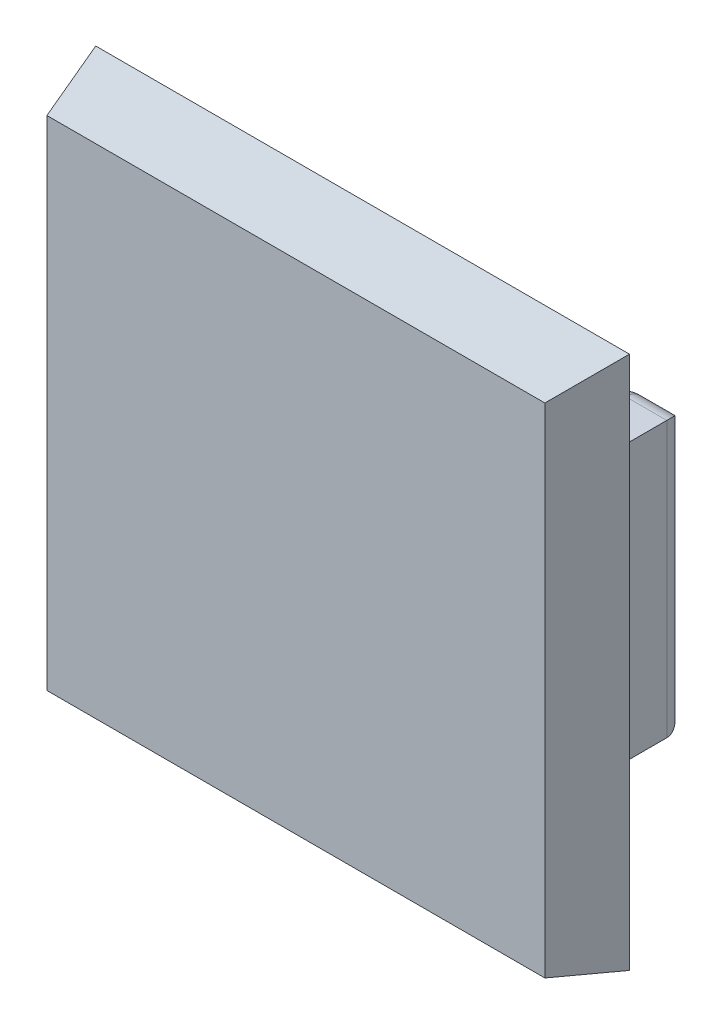
SolidWorks part; units mm, degrees
ref_plane "Front Plane" through (0, 0, 0) normal (0, 0, 1) x (1, 0, 0)
ref_plane "Top Plane" through (0, 0, 0) normal (0, 1, 0) x (1, 0, 0)
ref_plane "Right Plane" through (0, 0, 0) normal (1, 0, 0) x (0, 0, -1)
sketch "Sketch1" plane through (0, 0, 0) normal (0, 0, 1) x (1, 0, 0)
  line L1 (-10, 10) -> (10, 10)
  line L2 (-10, 10) -> (-10, -10)
  line L3 (-10, -10) -> (10, -10)
  line L4 (10, 10) -> (10, -10)
  line L5 (-10, 10) -> (10, -10) construction
  line L6 (-10, -10) -> (10, 10) construction
  point P0 (0, 0)
  dimension "D1" = 20
  dimension "D2" = 20
extrude "Boss-Extrude1" add sketch "Sketch1" along normal blind 2.5 draft 15
sketch "Sketch2" plane through (0, 0, 0) normal (0, 0, -1) x (-1, 0, 0)
  line L0 (10, 10) -> (10, -10) construction
  line L1 (-9, 9) -> (9, 9)
  line L2 (-9, 9) -> (-9, -9)
  line L3 (-9, -9) -> (9, -9)
  line L4 (9, 9) -> (9, -9)
  line L5 (-9, 9) -> (9, -9) construction
  line L6 (-9, -9) -> (9, 9) construction
  line L7 (10, -10) -> (-10, -10) construction
  point P0 (0, 0)
  dimension "D1" = 1
  dimension "D2" = 1
extrude "Cut-Extrude1" cut sketch "Sketch2" against normal blind 0.85
sketch "Sketch3" plane through (0, 0, 0.85) normal (0, 0, -1) x (-1, 0, 0)
  circle A0 centre (0, 0) radius 2
  dimension "D1" = 4
extrude "Boss-Extrude2" add sketch "Sketch3" along normal blind 8.2 draft 1.5
chamfer "Chamfer1" distance 2 distance2 0.5 1 edges at (-1.7853, 0, -7.35)
fillet "Fillet1" radius 0.5 2 edges at (1.8376, 0, -5.3507) (-1.2853, 0, -7.35)
sketch "Sketch4" plane through (0, 0, -7.35) normal (0, 0, -1) x (-1, 0, 0)
  line L0 (0, 3.136) -> (0, -3.0241)
  line L1 (-3.0348, 0) -> (3.2574, 0)
extrude "Cut-Extrude-Thin1" cut sketch "Sketch4" against normal up to surface (8.2 mm away) draft 1 thin
sketch "Sketch5" plane through (0, 0, 0.85) normal (0, 0, -1) x (-1, 0, 0)
  line L0 (0, 0) -> (4, 0) construction
  line L1 (4, 2.8) -> (4, -2.8)
  line L2 (4, -2.8) -> (6, -5.15)
  line L3 (8, -5.15) -> (8, 5.15)
  line L4 (6, 5.15) -> (4, 2.8)
  line L5 (10, 10) -> (10, -10) construction
  line L6 (6, 5.15) -> (8, 5.15)
  line L7 (6, -5.15) -> (8, -5.15)
  point P6 (4, 0)
  dimension "D1" = 10.3
  dimension "D2" = 4
  dimension "D3" = 2
  dimension "D4" = 5.6
  dimension "D5" = 2
extrude "Boss-Extrude3" add sketch "Sketch5" along normal blind 5
fillet "Fillet2" radius 1 4 edges at (-4, 2.8, -1.65) (-4, -2.8, -1.65) (-6, 5.15, -1.65) (-6, -5.15, -1.65)
fillet "Fillet3" radius 0.75 10 edges at (-7.231, 5.15, -4.15) (-6.0426, 5.0578, -4.15) (-4.9695, 3.9392, -4.15) (-4.0615, 2.7774, -4.15) (-4, 0, -4.15) (-4.0615, -2.7774, -4.15) (-4.9695, -3.9392, -4.15) (-6.0426, -5.0578, -4.15) (-8, 0, -4.15) (-7.231, -5.15, -4.15)
sketch "Sketch6" plane through (0, 0, -4.15) normal (0, 0, -1) x (-1, 0, 0)
  line L12 (7, -4.15) -> (7, 4.15)
  line L13 (7, 4.15) -> (6.4621, 4.15)
  line L14 (6.4621, 4.15) -> (5, 2.4321)
  line L15 (5, 2.4321) -> (5, -2.4321)
  line L16 (5, -2.4321) -> (6.4621, -4.15)
  line L17 (6.4621, -4.15) -> (7, -4.15)
  line L18 (7, -4.15) -> (7, 4.15)
  line L19 (7, 4.15) -> (6.4621, 4.15)
  line L20 (6.4621, 4.15) -> (5, 2.4321)
  line L21 (5, 2.4321) -> (5, -2.4321)
  line L22 (5, -2.4321) -> (6.4621, -4.15)
  line L23 (6.4621, -4.15) -> (7, -4.15)
  dimension "D1" = 0.25
extrude "Cut-Extrude2" cut sketch "Sketch6" against normal up to surface (5 mm away) up to face at (0.8577, 0.8577, 0.85)
mirror "Mirror1" about plane through (0, 0, 0) normal (1, 0, 0) of "Fillet2", "Boss-Extrude3", "Fillet3", "Cut-Extrude2"
